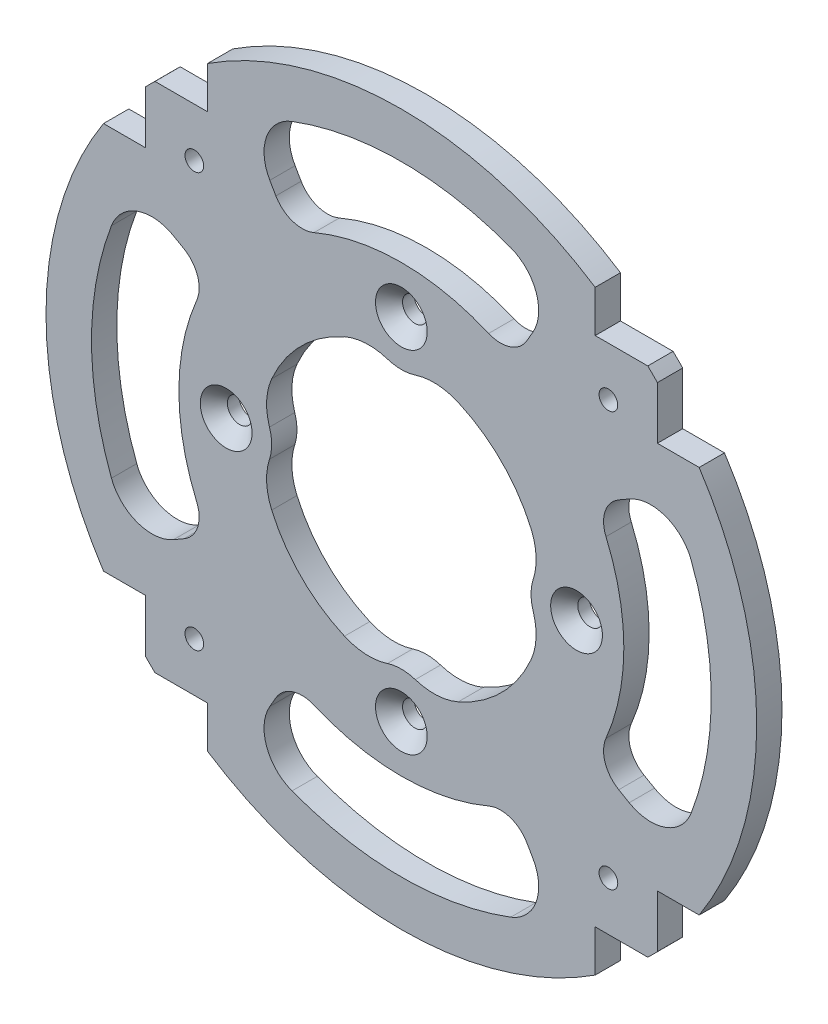
SolidWorks part; units mm, degrees
ref_plane "Front Plane" through (0, 0, 0) normal (0, 0, 1) x (1, 0, 0)
ref_plane "Top Plane" through (0, 0, 0) normal (0, 1, 0) x (1, 0, 0)
ref_plane "Right Plane" through (0, 0, 0) normal (1, 0, 0) x (0, 0, -1)
sketch "Sketch1" plane through (0, 0, 0) normal (0, 0, 1) x (1, 0, 0)
  line L0 (0, 0) -> (23.55, 0) construction
  line L1 (0, 0) -> (0, 1249.0795) construction
  line L2 (0, 0) -> (0, -63.25) construction
  line L3 (0, 0) -> (-26.743, -38.193) construction
  line L4 (0, 0) -> (-60, 0) construction
  line L5 (55.3014, 20.561) -> (0, 0) construction
  line L6 (-26, 26) -> (26, 26) construction
  line L7 (-26, 26) -> (-26, -26) construction
  line L8 (-26, -26) -> (26, -26) construction
  line L9 (26, 26) -> (26, -26) construction
  line L10 (0, 0) -> (0, -60) construction
  line L11 (-26, 26) -> (26, -26) construction
  line L12 (0, 0) -> (0, 60) construction
  line L13 (-26, -26) -> (26, 26) construction
  line L14 (0, 0) -> (28.25, -48.9304) construction
  circle A0 centre (0, 0) radius 22 construction
  circle A1 centre (22, 0) radius 1.55
  circle A2 centre (26, 26) radius 1.175
  circle A3 centre (-26, 26) radius 1.175
  circle A4 centre (-26, -26) radius 1.175
  circle A5 centre (26, -26) radius 1.175
  circle A6 centre (0, 0) radius 43.625 construction
  circle A7 centre (0, -22) radius 1.55
  circle A11 centre (-22, 0) radius 1.55
  circle A15 centre (0, 22) radius 1.55
  arc A16 (-22.7717, -38.3776) -> (19.369, -40.2024) centre (0, 0) ccw
  arc A18 (-2.379, 44.5615) -> (42.4989, 13.6102) centre (0, 0) ccw
  arc A21 (25.1318, -36.8752) -> (2.379, 44.5615) centre (0, 0) ccw
  arc A22 (-23.7737, -37.7651) -> (-27.3565, -35.2564) centre (-26.743, -38.193) ccw construction
  arc A23 (-9.2286, 43.6603) -> (9.2286, 43.6603) centre (0, 1249.0795) ccw construction
  arc A24 (24.1796, -37.5065) -> (20.3918, -39.6934) centre (23.3125, -40.3784) ccw construction
  arc A27 (41.0676, 17.4597) -> (-28.2747, -34.5243) centre (0, 0) ccw
  arc A38 (-1.7487, 16.5591) -> (1.7487, 16.5591) centre (0, 22) ccw
  arc A39 (16.5591, 1.7487) -> (16.5591, -1.7487) centre (22, 0) ccw
  arc A40 (1.7487, -16.5591) -> (-1.7487, -16.5591) centre (0, -22) ccw
  arc A41 (-16.5591, -1.7487) -> (-16.5591, 1.7487) centre (-22, 0) ccw
  arc A42 (-7.1407, 16.2831) -> (-16.2831, 7.1407) centre (0, 0) ccw
  arc A43 (16.2831, 7.1407) -> (7.1407, 16.2831) centre (0, 0) ccw
  arc A44 (7.1407, -16.2831) -> (16.2831, -7.1407) centre (0, 0) ccw
  arc A45 (-16.2831, -7.1407) -> (-7.1407, -16.2831) centre (0, 0) ccw
  arc A46 (-1.7487, 16.5591) -> (-7.1407, 16.2831) centre (-4.0804, 9.3046) ccw
  arc A47 (-16.2831, 7.1407) -> (-16.5591, 1.7487) centre (-9.3046, 4.0804) ccw
  arc A48 (-16.2831, -7.1407) -> (-16.5591, -1.7487) centre (-9.3046, -4.0804) cw
  arc A49 (-7.1407, -16.2831) -> (-1.7487, -16.5591) centre (-4.0804, -9.3046) ccw
  arc A50 (1.7487, -16.5591) -> (7.1407, -16.2831) centre (4.0804, -9.3046) ccw
  arc A51 (16.5591, -1.7487) -> (16.2831, -7.1407) centre (9.3046, -4.0804) cw
  arc A52 (16.2831, 7.1407) -> (16.5591, 1.7487) centre (9.3046, 4.0804) cw
  arc A53 (1.7487, 16.5591) -> (7.1407, 16.2831) centre (4.0804, 9.3046) cw
  point P5 (0, 0)
  point P49 (0, 0)
  point P69 (54.763, 5.1)
  point P88 (-17.4424, -3.4482)
  point P93 (3.4482, -17.4424)
  point P98 (17.4424, 3.4482)
  dimension "D1" = 44
  dimension "D2" = 3.1
  dimension "D3" = 52
  dimension "D4" = 2.35
  dimension "D9" = 1
  dimension "D11" = 150
  dimension "D12" = 90
  dimension "D13" = 11.43
  dimension "D14" = 17.78
  dimension "D15" = 7.62
  dimension "D17" = 6
  dimension "D5" = 87.25
  dimension "D16" = 145
  dimension "D7" = 4
extrude "Boss-Extrude1" add sketch "Sketch1" along normal blind 3.175 contours A1 A7 A11 A15 A38 A53 A43 A52 A39 A51 A44 A50 A40 A49 A45 A48 A41 A47 A42 A46 | A18 | A18 | A27 | A21 region at (-24.8719, -35.5207, 0)
sketch "Sketch3" plane through (0, 0, 3.175) normal (0, 0, 1) x (1, 0, 0)
  line L0 (-1000, 0) -> (49000, 0) construction
  line L1 (-54.7989, 36.8635) -> (-32.153, 36.8635)
  line L2 (-54.7989, 36.8635) -> (-54.7989, 24.3413)
  line L3 (-54.7989, 24.3413) -> (-32.153, 24.3413)
  line L4 (-32.153, 36.8635) -> (-32.153, 24.3413)
  line L5 (-54.7989, 36.8635) -> (-32.153, 24.3413) construction
  line L6 (-54.7989, 24.3413) -> (-32.153, 36.8635) construction
  line L7 (0, -1000) -> (0, 49000) construction
  line L8 (-54.7989, -36.8635) -> (-54.7989, -24.3413)
  line L9 (-54.7989, -36.8635) -> (-32.153, -36.8635)
  line L10 (-32.153, -36.8635) -> (-32.153, -24.3413)
  line L11 (-54.7989, -24.3413) -> (-32.153, -24.3413)
  line L12 (32.153, -36.8635) -> (32.153, -24.3413)
  line L13 (54.7989, -36.8635) -> (32.153, -36.8635)
  line L14 (54.7989, -36.8635) -> (54.7989, -24.3413)
  line L15 (54.7989, -24.3413) -> (32.153, -24.3413)
  line L16 (32.153, 36.8635) -> (32.153, 24.3413)
  line L17 (54.7989, 24.3413) -> (32.153, 24.3413)
  line L18 (54.7989, 36.8635) -> (32.153, 36.8635)
  line L19 (54.7989, 36.8635) -> (54.7989, 24.3413)
  line L20 (0, 0) -> (35355.3391, 35355.3391) construction
  line L21 (0, 0) -> (-35355.3391, 35355.3391) construction
  line L22 (-36.8635, -54.7989) -> (-24.3413, -54.7989)
  line L23 (-36.8635, -54.7989) -> (-36.8635, -32.153)
  line L24 (-36.8635, -32.153) -> (-24.3413, -32.153)
  line L25 (-24.3413, -54.7989) -> (-24.3413, -32.153)
  line L26 (-36.8635, 32.153) -> (-24.3413, 32.153)
  line L27 (-36.8635, 54.7989) -> (-36.8635, 32.153)
  line L28 (-36.8635, 54.7989) -> (-24.3413, 54.7989)
  line L29 (-24.3413, 54.7989) -> (-24.3413, 32.153)
  line L30 (36.8635, 54.7989) -> (24.3413, 54.7989)
  line L31 (36.8635, 54.7989) -> (36.8635, 32.153)
  line L32 (36.8635, 32.153) -> (24.3413, 32.153)
  line L33 (24.3413, 54.7989) -> (24.3413, 32.153)
  line L34 (36.8635, -54.7989) -> (24.3413, -54.7989)
  line L35 (24.3413, -54.7989) -> (24.3413, -32.153)
  line L36 (36.8635, -32.153) -> (24.3413, -32.153)
  line L37 (36.8635, -54.7989) -> (36.8635, -32.153)
  point P0 (-43.4759, 30.6024)
  circle M47 centre (0, 0) radius 44.625
extrude "Cut-Extrude2" cut sketch "Sketch3" against normal through all contours L29 L28 L27 L1 L4 L26 | L27 L1 L2 L3 L4 L26 | L30 L33 L32 L16 L18 L31 | L31 L32 L16 L17 L19 L18 | L37 L13 L14 L15 L12 L36 | L34 L37 L13 L12 L36 L35 | L22 L25 L24 L10 L9 L23 | L11 L10 M47 | L25 L24 M47 | L36 L35 M47 | L15 L12 M47 | L33 L32 M47 | L17 L16 M47 | L4 L3 M47 | L29 L26 M47 | L10 L11 L8 L9 region at (-45.0179, 30.5488, 3.175) region at (-30.5488, 45.0179, 3.175) region at (-33.9596, 26.6125, 3.175) region at (-33.9596, -26.6125, 3.175) region at (-26.6125, 33.9596, 3.175) region at (26.6125, 33.9596, 3.175) region at (30.5488, 45.0179, 3.175) region at (-30.5488, -45.0179, 3.175) region at (-26.6125, -33.9596, 3.175) region at (45.0179, 30.5488, 3.175) region at (33.9596, 26.6125, 3.175) region at (30.5488, -45.0179, 3.175) region at (26.6125, -33.9596, 3.175) region at (45.0179, -30.5488, 3.175) region at (33.9596, -26.6125, 3.175)
sketch "Sketch2" plane through (0, 0, 3.175) normal (0, 0, 1) x (1, 0, 0)
  line L0 (0, 0) -> (0, 27.94) construction
  line L1 (-16.5187, 28.6113) -> (-15.7603, 27.2976)
  line L2 (15.7603, 27.2976) -> (16.5187, 28.6113)
  line L3 (-26, 26) -> (-16.5187, 28.6113) construction
  line L4 (0, 22) -> (0, 0) construction
  line L5 (16.5187, 28.6113) -> (26, 26) construction
  arc A0 (-10.9654, 25.6983) -> (10.9654, 25.6983) centre (0, 0) cw
  arc A1 (-13.733, 36.406) -> (13.733, 36.406) centre (0, 0) cw
  arc A2 (10.9654, 25.6983) -> (15.7603, 27.2976) centre (12.4607, 29.2026) ccw
  arc A3 (16.5187, 28.6113) -> (13.733, 36.406) centre (11.8167, 31.326) ccw
  arc A4 (-13.733, 36.406) -> (-16.5187, 28.6113) centre (-11.8167, 31.326) ccw
  arc A5 (-10.9654, 25.6983) -> (-15.7603, 27.2976) centre (-12.4607, 29.2026) cw
  arc A7 (16.2831, 7.1407) -> (7.1407, 16.2831) centre (0, 0) ccw construction
  point P10 (0, 27.94)
  dimension "D2" = 38.91
  dimension "D3" = 10.16
  dimension "D5" = 3.81
  dimension "D1" = 5.08
  dimension "D4" = 30
extrude "Cut-Extrude1" cut sketch "Sketch2" against normal through all
pattern_circular "CirPattern1" count 4 over 360 about axis through (0, 0, 3.175) along (0, 0, -1) of "Cut-Extrude1"
fillet "Fillet1" [suppressed] radius 3.81
chamfer "Chamfer1" distance 1.7 angle 45 4 edges at (-20.45, 0, 3.175) (1.55, -22, 3.175) (23.55, 0, 3.175) (1.55, 22, 3.175)
ref_axis "Axis1" [suppressed] through (0, 0, 0) along (0, 0, 1)
